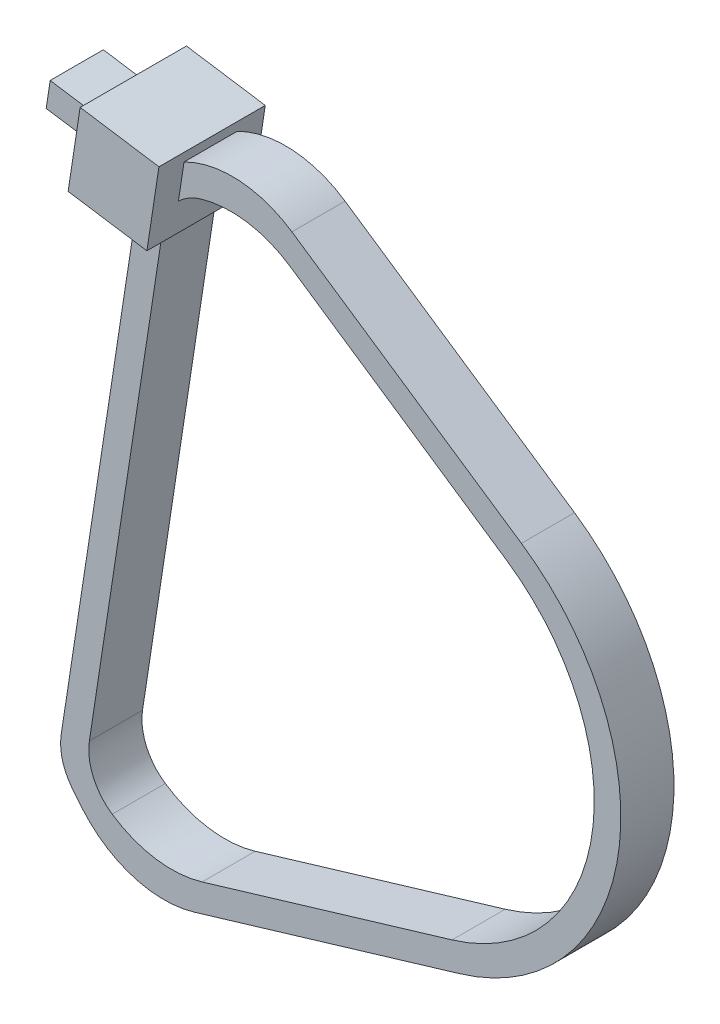
SolidWorks part; units mm, degrees
ref_plane "Front Plane" through (0, 0, 0) normal (0, 0, 1) x (1, 0, 0)
ref_plane "Top Plane" through (0, 0, 0) normal (0, 1, 0) x (1, 0, 0)
ref_plane "Right Plane" through (0, 0, 0) normal (1, 0, 0) x (0, 0, -1)
sketch "Sketch1" plane through (0, 0, 0) normal (0, 0, 1) x (1, 0, 0)
  line L0 (-7.2571, -9.9999) -> (2.1499, -7.1853)
  line L1 (2.4365, -8.1433) -> (-7.5484, -11.1309)
  line L2 (0, 0) -> (-9.6189, 1.4705) construction
  line L3 (-8.8066, 6.7838) -> (-10.4311, -3.8428) construction
  line L4 (-9.6189, 1.4705) -> (15.1759, -2.32) construction
  line L5 (-9.6189, 1.4705) -> (-17.9253, 2.7403) construction
  line L6 (4.7582, 7.0434) -> (-3.878, 12.8777)
  line L7 (-3.938, 11.7114) -> (4.1984, 6.2148)
  line L8 (-11.4996, -7.5233) -> (-8.7266, 10.6154)
  line L9 (-12.5596, -7.8398) -> (-9.6437, 11.2341)
  line L10 (-14.9081, -33.1275) -> (-10.3745, -3.4721) construction
  line L11 (-10.3745, -3.4721) -> (-8.1077, 11.3556) construction
  arc A0 (-12.5596, -7.8398) -> (-12.1677, -9.3616) centre (-10.5826, -8.142) ccw
  arc A1 (-8.2726, 12.9327) -> (-8.815, 12.5693) centre (0, 0) ccw
  circle A2 centre (0, 0) radius 7.5 construction
  arc A3 (2.4365, -8.1433) -> (4.7582, 7.0434) centre (0, 0) ccw
  arc A4 (-7.5484, -11.1309) -> (-11.7587, -9.8704) centre (-8.695, -7.2987) cw
  arc A5 (-7.2571, -9.9999) -> (-10.6414, -9.4833) centre (-8.4037, -6.1678) cw
  arc A6 (-3.938, 11.7114) -> (-7.3221, 12.2295) centre (-6.1772, 8.3968) ccw
  arc A7 (-3.878, 12.8777) -> (-8.2726, 12.9327) centre (-6.1172, 9.5631) ccw
  arc A8 (2.1499, -7.1853) -> (4.1984, 6.2148) centre (0, 0) ccw
  arc A9 (-12.1677, -9.3616) -> (-11.7587, -9.8704) centre (0, 0) ccw
  arc A10 (-11.4996, -7.5233) -> (-10.6414, -9.4833) centre (-9.5226, -7.8256) ccw
  arc A11 (-8.7266, 10.6154) -> (-7.3221, 12.2295) centre (-6.7496, 10.3132) cw
  arc A12 (-9.6437, 11.2341) -> (-8.815, 12.5693) centre (-7.6666, 10.9319) cw
  point P32 (-12.6835, -8.65)
  point P35 (-11.6497, -8.5052)
  point P38 (-8.5765, 11.5973)
  dimension "D1" = 2
  dimension "D3" = 1
  dimension "D4" = 4
  dimension "D5" = 2.1499
  dimension "D6" = 1
  dimension "D7" = 0.5
  dimension "D8" = 10.4242
  dimension "D2" = 1
  dimension "D9" = 11.3523
extrude "Boss-Extrude1" add sketch "Sketch1" along normal blind 2 from offset 1.25 offset against normal yes
sketch "Sketch2" plane through (0, 0, 0.75) normal (0, 0, 1) x (1, 0, 0)
  line L1 (-8.3349, 10.5308) -> (-11.3005, 10.9841)
  line L2 (-8.3349, 10.5308) -> (-7.8816, 13.4963)
  line L3 (-7.8816, 13.4963) -> (-10.8471, 13.9497)
  line L4 (-11.3005, 10.9841) -> (-10.8471, 13.9497)
  line L5 (-8.3349, 10.5308) -> (-10.8471, 13.9497) construction
  line L6 (-7.8816, 13.4963) -> (-11.3005, 10.9841) construction
  line L9 (-8.1077, 11.3556) -> (-2.8185, 45.9537) construction
  line L10 (-8.7266, 10.6154) -> (-11.4996, -7.5233) construction
  line L11 (-9.6437, 11.2341) -> (-12.5596, -7.8398) construction
  point P0 (-9.591, 12.2402)
  dimension "D1" = 3
  dimension "D2" = 0.1
  dimension "D3" = 3
  dimension "D4" = 12.2402
extrude "Boss-Extrude2" add sketch "Sketch2" along normal blind 1 and the other way blind 3
sketch "Sketch3" plane through (-12.6833, 1.939, 0) normal (-0.9885, 0.1511, 0) x (0, 0, 1)
  line L0 (0.75, 11.7741) -> (0.75, 10.3747) construction
  line L1 (-1.25, 10.1502) -> (0.75, 10.1502)
  line L2 (-1.25, 10.1502) -> (-1.25, 11.1502)
  line L3 (-1.25, 11.1502) -> (0.75, 11.1502)
  line L4 (0.75, 10.1502) -> (0.75, 11.1502)
  line L5 (-1.25, 10.1502) -> (0.75, 11.1502) construction
  line L6 (-1.25, 11.1502) -> (0.75, 10.1502) construction
  line L7 (-1.25, 9.1502) -> (-1.25, -9.6477) construction
  line L8 (-2.25, 9.1502) -> (1.75, 9.1502) construction
  point P0 (-0.25, 10.6502)
  dimension "D1" = 1
  dimension "D2" = 1.5
extrude "Boss-Extrude3" add sketch "Sketch3" along normal blind 2
